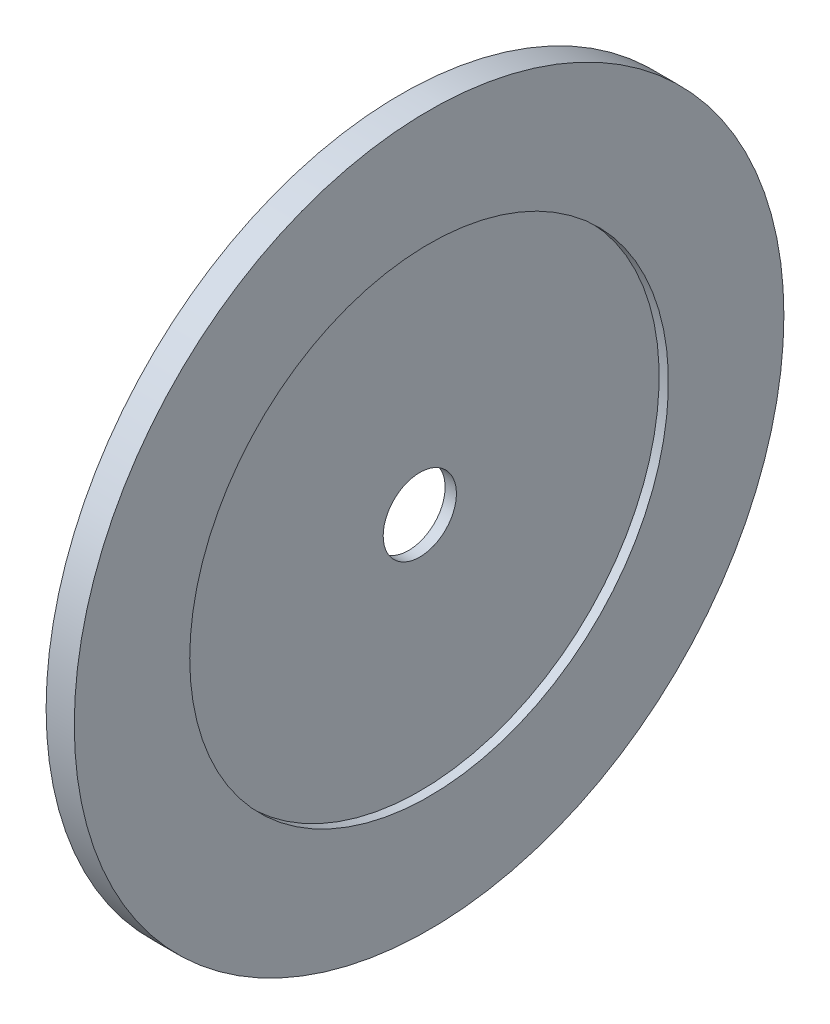
SolidWorks part; units mm, degrees
ref_plane "Front Plane" through (0, 0, 0) normal (0, 0, 1) x (1, 0, 0)
ref_plane "Top Plane" through (0, 0, 0) normal (0, 1, 0) x (1, 0, 0)
ref_plane "Right Plane" through (0, 0, 0) normal (1, 0, 0) x (0, 0, -1)
sketch "Sketch1" plane through (0, 0, 0) normal (0, 0, 1) x (1, 0, 0)
  line L0 (0, 0) -> (58.591, 0) construction
  line L2 (0, 0) -> (19, 0)
  line L3 (0, 0) -> (0, 2.5)
  line L4 (0, 2.5) -> (19, 2.5)
  line L5 (19, 0) -> (19, 2.5)
  line L6 (6.7938, 2.5) -> (6.7938, 6)
  line L11 (6.7938, 6) -> (10.7938, 6)
  line L16 (12.8938, 6) -> (12.8938, 3)
  line L17 (12.8938, 3) -> (13.8938, 3)
  line L18 (13.8938, 3) -> (13.8938, 2.5)
  line L19 (13.8938, 2.5) -> (6.7938, 2.5)
  line L22 (13.8938, 2.5) -> (16.3938, 2.5)
  line L23 (13.8938, 2.5) -> (13.8938, 4)
  line L24 (13.8938, 4) -> (16.3938, 4)
  line L25 (16.3938, 2.5) -> (16.3938, 4)
  line L27 (6.7938, 6) -> (10.7938, 6)
  line L28 (6.7938, 6) -> (6.7938, 9)
  line L29 (6.7938, 9) -> (10.7938, 9)
  line L30 (10.7938, 6) -> (10.7938, 9)
  line L31 (6.7938, 9) -> (6.7938, 8.5)
  line L32 (6.7938, 8.5) -> (5, 8.5)
  line L33 (7.8969, 22.001) -> (7.8969, 12.476) construction
  line L34 (5, 12.476) -> (10.7938, 12.476)
  line L35 (10.7938, 12.476) -> (10.7938, 9)
  line L36 (5, 7.5) -> (3, 7.5)
  line L37 (5, 8.5) -> (5, 12.476)
  line L38 (5, 7.5) -> (5, 14)
  line L39 (5, 14) -> (3, 14)
  line L40 (3, 7.5) -> (3, 14)
  line L41 (5, 22.001) -> (10.7938, 22.001)
  line L42 (5, 22.001) -> (5, 30.1625)
  line L43 (5, 30.1625) -> (10.7938, 30.1625)
  line L44 (10.7938, 22.001) -> (10.7938, 30.1625)
  line L45 (13.8938, 4) -> (13.8938, 22.001)
  line L49 (16.8938, 22.001) -> (16.8938, 8)
  line L50 (16.8938, 8) -> (17.8938, 8)
  line L51 (22.8938, 7.5) -> (22.8938, 6.5)
  line L54 (16.3938, 4) -> (13.8938, 4)
  line L55 (17.8938, 8) -> (17.8938, 7.5)
  line L56 (17.8938, 7.5) -> (22.8938, 7.5)
  line L57 (13.8938, 22.001) -> (16.8938, 22.001)
  line L58 (16.3938, 3.5) -> (19.8938, 3.5)
  line L59 (28.8938, 14) -> (26.3938, 11.5)
  line L60 (4, 31.75) -> (17.8938, 31.75)
  line L61 (17.8938, 7.5) -> (22.8938, 7.5)
  line L62 (17.8938, 7.5) -> (17.8938, 12)
  line L63 (17.8938, 12) -> (22.8938, 12)
  line L64 (22.8938, 7.5) -> (22.8938, 12)
  line L65 (17.8938, 31.75) -> (17.8938, 12)
  line L66 (22.8938, 11.5) -> (26.3938, 11.5)
  line L67 (32.8938, 23) -> (29.8938, 20)
  line L68 (33.8938, 31.5) -> (36.0538, 33.66)
  line L69 (28.8938, 14) -> (28.8938, 15)
  line L70 (28.8938, 15) -> (21.8938, 15)
  line L71 (21.8938, 15) -> (21.8938, 16)
  line L72 (21.8938, 16) -> (20.8938, 16)
  line L73 (20.8938, 16) -> (20.8938, 41)
  line L74 (19.8938, 40) -> (9.8938, 40)
  line L75 (9.8938, 40) -> (4, 40)
  line L76 (20.8938, 41) -> (19.8938, 41)
  line L77 (21.8938, 15) -> (28.8938, 15)
  line L78 (21.8938, 15) -> (21.8938, 21)
  line L79 (21.8938, 21) -> (28.8938, 21)
  line L80 (28.8938, 15) -> (28.8938, 21)
  line L81 (9.8938, 40) -> (19.8938, 40)
  line L82 (9.8938, 40) -> (9.8938, 50)
  line L83 (9.8938, 50) -> (19.8938, 50)
  line L84 (19.8938, 40) -> (19.8938, 50)
  line L85 (4, 40) -> (4, 31.75)
  line L86 (12.8938, 3) -> (12.8938, 2.5)
  line L87 (29.8938, 20) -> (28.8938, 20)
  line L88 (21.8938, 21) -> (21.8938, 63.001)
  line L89 (21.8938, 63.001) -> (24.8938, 63.001)
  line L90 (24.8938, 63.001) -> (24.8938, 26)
  line L91 (24.8938, 26) -> (25.8938, 26)
  line L92 (9.8938, 49) -> (8.65, 49)
  line L93 (8.65, 49) -> (8.65, 53.476)
  line L94 (8.65, 53.476) -> (19.8938, 53.476)
  line L95 (19.8938, 53.476) -> (19.8938, 50)
  line L96 (14.2719, 63.001) -> (14.2719, 53.476) construction
  line L97 (8.65, 63.001) -> (19.8938, 63.001)
  line L98 (8.65, 63.001) -> (8.65, 68.2625)
  line L99 (8.65, 68.2625) -> (19.8938, 68.2625)
  line L100 (19.8938, 63.001) -> (19.8938, 68.2625)
  line L101 (12.8938, 6) -> (11.8938, 6)
  line L102 (8.65, 42.5) -> (4.65, 42.5)
  line L103 (8.65, 42.5) -> (8.65, 55)
  line L104 (8.65, 55) -> (4.65, 55)
  line L105 (4.65, 42.5) -> (4.65, 55)
  line L106 (25.8938, 26) -> (25.8938, 25)
  line L107 (25.8938, 25) -> (32.8938, 25)
  line L108 (32.8938, 25) -> (32.8938, 23)
  line L109 (0, 0) -> (-2, 0)
  line L110 (0, 0) -> (0, 11)
  line L111 (25.8938, 25) -> (32.8938, 25)
  line L112 (25.8938, 25) -> (25.8938, 32.5)
  line L113 (25.8938, 32.5) -> (32.8938, 32.5)
  line L114 (32.8938, 25) -> (32.8938, 32.5)
  line L115 (33.8938, 31.5) -> (32.8938, 31.5)
  line L116 (25.8938, 32.5) -> (25.8938, 69.85)
  line L117 (25.8938, 69.85) -> (-1.35, 69.85)
  line L118 (-1.35, 69.85) -> (-1.35, 76.2)
  line L119 (-1.35, 76.2) -> (27.7938, 76.2)
  line L120 (0, 11) -> (-2, 11)
  line L121 (36.0538, 53.975) -> (28.1163, 53.975)
  line L123 (27.7938, 76.2) -> (36.0538, 67.94)
  line L124 (36.0538, 67.94) -> (36.0538, 33.66)
  line L125 (-2, 0) -> (-2, 11)
  line L126 (36.0538, 47.625) -> (28.1163, 47.625)
  line L127 (28.1163, 53.975) -> (28.1163, 47.625)
  line L128 (6.7938, 2.5) -> (6.7938, 0)
  line L129 (-0.35, 63.001) -> (-0.35, 31)
  line L132 (4.65, 63.001) -> (-0.35, 63.001)
  line L134 (-0.35, 31) -> (-1.35, 31)
  line L135 (-1.35, 31) -> (-1.35, 30)
  line L136 (-1.35, 30) -> (-11.35, 30)
  line L137 (-11.35, 30) -> (-11.35, 25.4)
  line L138 (-11.35, 25.4) -> (-2, 25.4)
  line L139 (-2, 25.4) -> (-2, 11.5)
  line L140 (-1.35, 76.2) -> (-4.35, 76.2)
  line L141 (-1.35, 30) -> (-11.35, 30)
  line L142 (-1.35, 30) -> (-1.35, 39)
  line L143 (-1.35, 39) -> (-11.35, 39)
  line L144 (-11.35, 30) -> (-11.35, 39)
  line L145 (-4.35, 76.2) -> (-12.35, 68.2)
  line L146 (-12.35, 68.2) -> (-12.35, 38)
  line L147 (-12.35, 38) -> (-11.35, 38)
  line L148 (-1.35, 39) -> (-1.35, 69.85)
  line L149 (11.8938, 6) -> (11.8938, 5.45)
  line L154 (-2, 11.5) -> (1, 11.5)
  line L155 (4.65, 60.6197) -> (23.7, 60.6197)
  line L160 (4.65, 60.6197) -> (4.65, 55.8572)
  line L161 (4.65, 55.8572) -> (23.7, 55.8572)
  line L166 (23.7, 60.6197) -> (23.7, 55.8572)
  line L167 (4.65, 60.6197) -> (23.7, 55.8572) construction
  line L172 (4.65, 55.8572) -> (23.7, 60.6197) construction
  line L173 (23.7, 62.2072) -> (24.8938, 62.2072)
  line L174 (11.8938, 5.45) -> (10.7938, 5.45)
  line L175 (10.7938, 5.45) -> (10.7938, 6)
  line L176 (23.7, 62.2072) -> (23.7, 54.2697)
  line L177 (23.7, 54.2697) -> (24.8938, 54.2697)
  line L178 (24.8938, 62.2072) -> (24.8938, 54.2697)
  line L179 (23.7, 62.2072) -> (24.8938, 54.2697) construction
  line L180 (23.7, 54.2697) -> (24.8938, 62.2072) construction
  line L181 (3, 19.6197) -> (15.7, 19.6197)
  line L182 (3, 19.6197) -> (3, 14.8572)
  line L183 (3, 14.8572) -> (15.7, 14.8572)
  line L184 (15.7, 19.6197) -> (15.7, 14.8572)
  line L185 (3, 19.6197) -> (15.7, 14.8572) construction
  line L186 (3, 14.8572) -> (15.7, 19.6197) construction
  line L187 (15.7, 21.2072) -> (16.8938, 21.2072)
  line L188 (15.7, 21.2072) -> (15.7, 13.2697)
  line L189 (15.7, 13.2697) -> (16.8938, 13.2697)
  line L190 (16.8938, 21.2072) -> (16.8938, 13.2697)
  line L191 (15.7, 21.2072) -> (16.8938, 13.2697) construction
  line L192 (15.7, 13.2697) -> (16.8938, 21.2072) construction
  line L193 (1, 11.5) -> (1, 6.5)
  line L194 (1, 6.5) -> (3, 6.5)
  line L195 (22.8938, 6.5) -> (19.8938, 3.5)
  line L196 (4.65, 63.001) -> (4.65, 42.5)
  line L197 (4.65, 42.5) -> (3, 42.5)
  line L198 (3, 42.5) -> (3, 6.5)
  line L199 (6.7938, 0) -> (12.8938, 0)
  line L200 (12.8938, 0) -> (12.8938, 2.5)
  line L201 (17.8938, 31.75) -> (17.8938, 35.875)
  line L202 (17.8938, 35.875) -> (20.8938, 35.875)
  line L203 (27.7938, 76.2) -> (25.8938, 69.85)
  point P7 (24.2969, 58.2385)
  point P131 (16.2969, 17.2385)
  point P135 (14.175, 58.2385)
  point P146 (9.35, 17.2385)
sketch "Sketch2" plane through (0, 0, 0) normal (0, 0, 1) x (1, 0, 0)
  line L0 (-1.35, 30) -> (-11.35, 30) construction
  line L1 (-2, 25.4) -> (-2, 11.5) construction
  line L2 (-11.35, 30) -> (-11.35, 25.4) construction
  line L3 (-11.35, 25.4) -> (-2, 25.4) construction
  line L4 (-2, 11.5) -> (1, 11.5) construction
  line L5 (1, 11.5) -> (1, 6.5) construction
  line L6 (1, 6.5) -> (3, 6.5) construction
  line L7 (3, 42.5) -> (3, 6.5) construction
  line L8 (4.65, 42.5) -> (3, 42.5) construction
  line L9 (4.65, 63.001) -> (4.65, 42.5) construction
  line L10 (4.65, 63.001) -> (-0.35, 63.001) construction
  line L11 (-0.35, 63.001) -> (-0.35, 31) construction
  line L12 (-0.35, 31) -> (-1.35, 31) construction
  line L13 (-1.35, 31) -> (-1.35, 30) construction
  line L14 (-1.35, 30) -> (-11.35, 30)
  line L15 (-2, 25.4) -> (-2, 11.5)
  line L16 (-11.35, 30) -> (-11.35, 25.4)
  line L17 (-11.35, 25.4) -> (-2, 25.4)
  line L18 (-2, 11.5) -> (1, 11.5)
  line L19 (1, 11.5) -> (1, 6.5)
  line L20 (1, 6.5) -> (3, 6.5)
  line L21 (3, 42.5) -> (3, 6.5)
  line L22 (4.65, 42.5) -> (3, 42.5)
  line L23 (4.65, 63.001) -> (4.65, 42.5)
  line L24 (4.65, 63.001) -> (-0.35, 63.001)
  line L25 (-0.35, 63.001) -> (-0.35, 31)
  line L26 (-0.35, 31) -> (-1.35, 31)
  line L27 (-1.35, 31) -> (-1.35, 30)
revolve "Revolve1" add sketch "Sketch2" angle 360 about L0 region at (0.1863, 34.915, 0)
